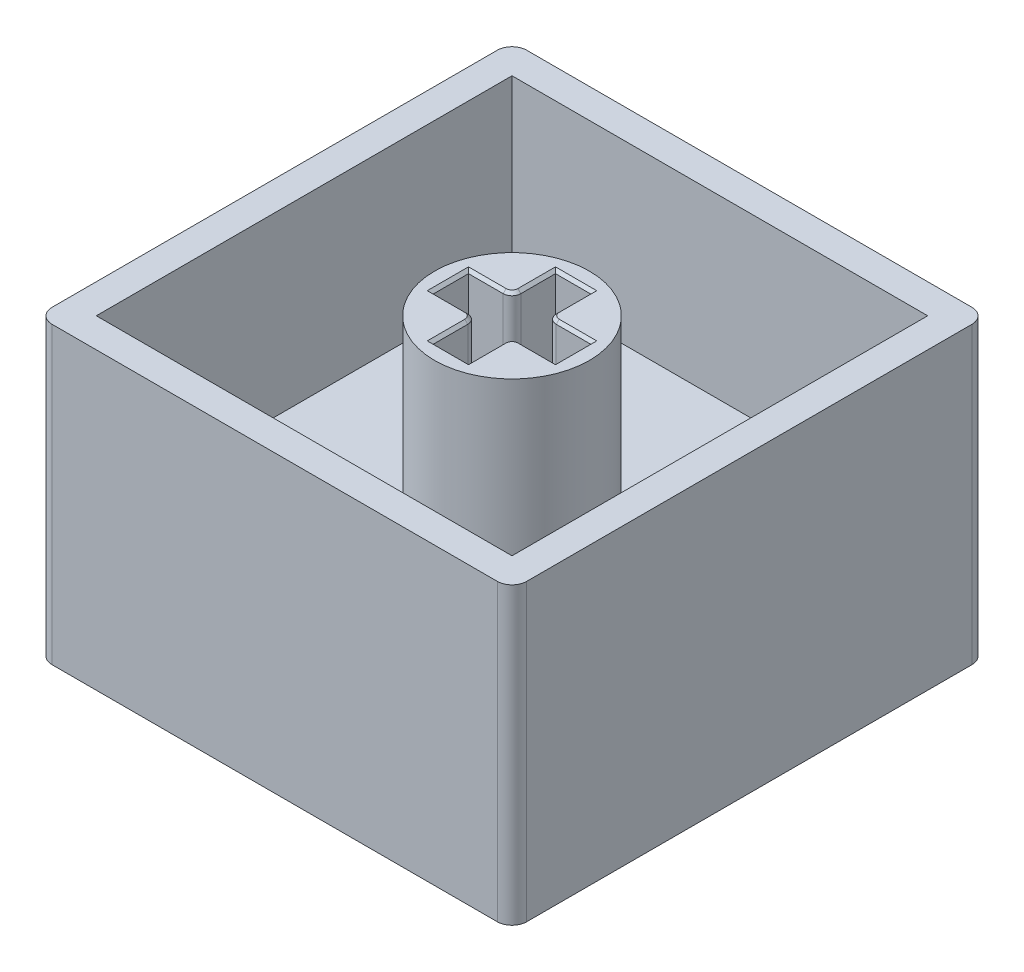
SolidWorks part; units mm, degrees
note: The reader was unsure of these and kept them because the rebuilt part matched: shared geometry of "Sketch1<2>".
ref_plane "Front Plane" through (0, 0, 0) normal (0, 0, 1) x (1, 0, 0)
ref_plane "Top Plane" through (0, 0, 0) normal (0, 1, 0) x (1, 0, 0)
ref_plane "Right Plane" through (0, 0, 0) normal (1, 0, 0) x (0, 0, -1)
sketch "Sketch1" plane through (0, 0, 0) normal (0, 1, 0) x (1, 0, 0)
  line L1 (-7.05, -7.05) -> (7.05, -7.05)
  line L2 (-7.05, -7.05) -> (-7.05, 7.05)
  line L3 (-7.05, 7.05) -> (7.05, 7.05)
  line L4 (7.05, -7.05) -> (7.05, 7.05)
  line L5 (-7.05, -7.05) -> (7.05, 7.05) construction
  line L6 (-7.05, 7.05) -> (7.05, -7.05) construction
  line L7 (-8.05, -8.05) -> (8.05, -8.05)
  line L8 (-8.05, -8.05) -> (-8.05, 8.05)
  line L9 (-8.05, 8.05) -> (8.05, 8.05)
  line L10 (8.05, -8.05) -> (8.05, 8.05)
  line L11 (-8.05, -8.05) -> (8.05, 8.05) construction
  line L12 (-8.05, 8.05) -> (8.05, -8.05) construction
  point P0 (0, 0)
  point P6 (0, 0)
  dimension "D2" = 14.1
extrude "Boss-Extrude1" add sketch "Sketch1" along normal blind 10
extrude "Boss-Extrude2" add sketch "Sketch1<2>" along normal blind 4 contours L1 L4 L3 L2
sketch "Sketch1<2>" plane through (0, 0, 0) normal (0, 1, 0) x (1, 0, 0) same geometry as "Sketch1"
sketch "Sketch2" plane through (0, 4, 0) normal (0, 1, 0) x (1, 0, 0)
  line L1 (-2.075, -0.6) -> (2.075, -0.6)
  line L2 (-2.075, -0.6) -> (-2.075, 0.6)
  line L3 (-2.075, 0.6) -> (2.075, 0.6)
  line L4 (2.075, -0.6) -> (2.075, 0.6)
  line L5 (-2.075, -0.6) -> (2.075, 0.6) construction
  line L6 (-2.075, 0.6) -> (2.075, -0.6) construction
  line L7 (0.6, -2.075) -> (-0.6, -2.075)
  line L8 (0.6, -2.075) -> (0.6, 2.075)
  line L9 (0.6, 2.075) -> (-0.6, 2.075)
  line L10 (-0.6, -2.075) -> (-0.6, 2.075)
  line L11 (0.6, -2.075) -> (-0.6, 2.075) construction
  line L12 (0.6, 2.075) -> (-0.6, -2.075) construction
  line L13 (-0.9, -0.9) -> (0.9, -0.9) construction
  line L14 (-0.9, -0.9) -> (-0.9, 0.9) construction
  line L15 (-0.9, 0.9) -> (0.9, 0.9) construction
  line L16 (0.9, -0.9) -> (0.9, 0.9) construction
  line L17 (-0.9, -0.9) -> (0.9, 0.9) construction
  line L18 (-0.9, 0.9) -> (0.9, -0.9) construction
  line L19 (-2.95, -2.2) -> (2.95, -2.2) construction
  line L20 (-2.95, -2.2) -> (-2.95, 2.2) construction
  line L21 (-2.95, 2.2) -> (2.95, 2.2) construction
  line L22 (2.95, -2.2) -> (2.95, 2.2) construction
  line L23 (-2.95, -2.2) -> (2.95, 2.2) construction
  line L24 (-2.95, 2.2) -> (2.95, -2.2) construction
  line L25 (-1.6, -2.2) -> (1.6, -2.2) construction
  line L26 (-1.6, -2.2) -> (-1.6, 2.2) construction
  line L27 (-1.6, 2.2) -> (1.6, 2.2) construction
  line L28 (1.6, -2.2) -> (1.6, 2.2) construction
  line L29 (-1.6, -2.2) -> (1.6, 2.2) construction
  line L30 (-1.6, 2.2) -> (1.6, -2.2) construction
  circle A0 centre (0, 0) radius 2.625
  arc A1 (-0.9, 0.6) -> (-0.6, 0.9) centre (-0.9, 0.9) ccw
  arc A2 (0.6, 0.9) -> (0.9, 0.6) centre (0.9, 0.9) ccw
  arc A3 (-0.6, -0.9) -> (-0.9, -0.6) centre (-0.9, -0.9) ccw
  arc A4 (0.9, -0.6) -> (0.6, -0.9) centre (0.9, -0.9) ccw
  dimension "D3" = 0.3
  dimension "D7" = 5.25
  dimension "D1" = 1.2
  dimension "D2" = 4.15
  dimension "D4" = 5.9
  dimension "D5" = 4.4
  dimension "D6" = 3.2
extrude "Boss-Extrude3" add sketch "Sketch2" along normal up to surface (6 mm away) contours A0 L1 A4 L8 L7 L10 A3 L2 L3 A1 L9 A2 L4 up to face at (0, 10, 0)
chamfer "Chamfer1" distance 0.1 angle 45 16 edges at (1.4875, 10, -0.6) (0.6879, 10, -0.6879) (0.6, 10, -1.4875) (-0.6, 10, -1.4875) (-0.6879, 10, -0.6879) (-1.4875, 10, -0.6) (-1.4875, 10, 0.6) (-0.6879, 10, 0.6879) (-0.6, 10, 1.4875) (0.6, 10, 1.4875) (0.6879, 10, 0.6879) (1.4875, 10, 0.6) (2.075, 10, 0) (0, 10, -2.075) (-2.075, 10, 0) (0, 10, 2.075)
fillet "Fillet1" radius 0.5 4 edges at (-8.05, 5, 8.05) (-8.05, 5, -8.05) (8.05, 5, -8.05) (8.05, 5, 8.05)
ref_plane "Plane1" through (0, 0, 2.625) normal (0, 0, 1) x (1, 0, 0)
equation "\"Outer Circle Dia\"= 5.25"
equation "\"Long X Length\"= 4.15"
equation "\"Short X Length\"= 1.2"
equation "\"Fillet Rad\"= 0.3"
equation "\"Keycap Height\"= 10"
equation "\"X Chamfer\"= 0.1"
equation "\"Outer Fillet\"= 0.5"
equation "\"Keyswitch Hole Length\"= 14.1"
equation "\"D2@Sketch1\"=\"Keyswitch Hole Length\""
equation "\"D1@Boss-Extrude1\"=\"Keycap Height\""
equation "\"D1@Sketch2\"=\"Short X Length\""
equation "\"D3@Sketch2\"=\"Fillet Rad\""
equation "\"D1@Chamfer1\"=\"X Chamfer\""
equation "\"D1@Fillet1\"=\"Outer Fillet\""
equation "\"D7@Sketch2\"=\"Outer Circle Dia\""
